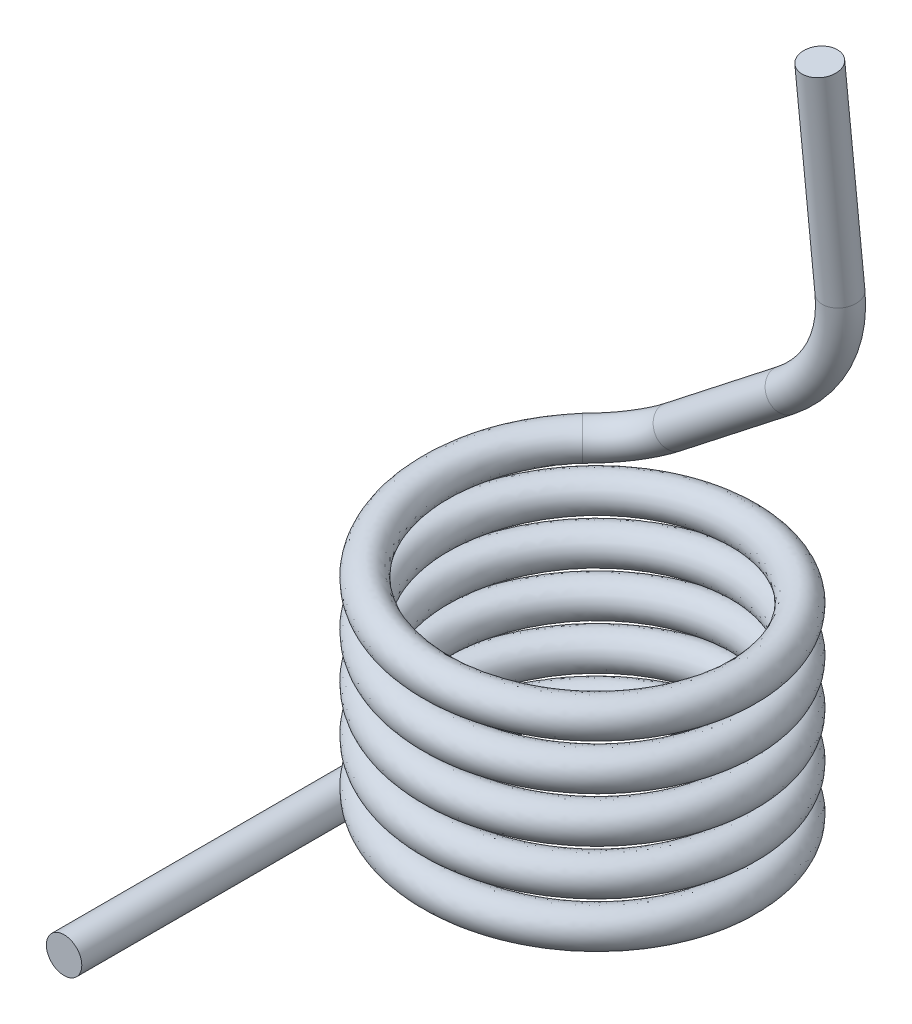
SolidWorks part; units mm, degrees
ref_plane "Front Plane" through (0, 0, 0) normal (0, 0, 1) x (1, 0, 0)
ref_plane "Top Plane" through (0, 0, 0) normal (0, 1, 0) x (1, 0, 0)
ref_plane "Right Plane" through (0, 0, 0) normal (1, 0, 0) x (0, 0, -1)
sketch "Sketch1" plane through (0, 0, 0) normal (0, 1, 0) x (1, 0, 0)
  circle A0 centre (0, 0) radius 24.13
  dimension "D1" = 48.26
curve "Helix/Spiral1" pitch 7.1437 height 36.6117 turns 5.125
sketch "Sketch2" plane through (0, 0, 0) normal (0, 0, 1) x (1, 0, 0)
  circle A0 centre (-24.13, 0) radius 2.7781
  spline S0 degree 3 poles (-24.13, 0) (-24.13, 0.1096) (-23.4483, 0.33) (-20.4662, 0.6596) (-15.7737, 0.9895) (-9.763, 1.3193) (-2.9364, 1.6492) (4.1356, 1.979) (10.862, 2.3088) (16.6806, 2.6387) (21.1053, 2.9685) (23.7661, 3.2984) (24.4408, 3.6282) (23.073, 3.958) (19.777, 4.2879) (14.8281, 4.6177) (8.6401, 4.9475) (1.73, 5.2774) (-5.3246, 5.6072) (-11.9343, 5.937) (-17.5466, 6.2669) (-21.6926, 6.5967) (-24.0256, 6.9265) (-24.3509, 7.2564) (-22.6411, 7.5862) (-19.0392, 7.916) (-13.8462, 8.2459) (-7.496, 8.5757) (-0.5194, 8.9056) (6.5006, 9.2354) (12.9774, 9.5652) (18.3696, 9.8951) (22.2266, 10.2249) (24.2262, 10.5547) (24.2012, 10.8846) (22.1537, 11.2144) (18.2547, 11.5442) (12.8302, 11.8741) (6.3335, 12.2039) (-0.6925, 12.5337) (-7.6606, 12.8636) (-13.9886, 13.1934) (-19.1475, 13.5232) (-22.7062, 13.8531) (-24.3674, 14.1829) (-23.9922, 14.5128) (-21.6119, 14.8426) (-17.4255, 15.1724) (-11.7828, 15.5023) (-5.1555, 15.8321) (1.9027, 16.1619) (8.8019, 16.4918) (14.9655, 16.8216) (19.8784, 17.1514) (23.1301, 17.4813) (24.4488, 17.8111) (23.7243, 18.1409) (21.0171, 18.4708) (16.5535, 18.8006) (10.7066, 19.1304) (3.9648, 19.4603) (-3.1082, 19.7901) (-9.9215, 20.12) (-15.9057, 20.4498) (-20.5606, 20.7796) (-23.4973, 21.1095) (-24.4702, 21.4393) (-23.3982, 21.7691) (-20.3708, 22.099) (-15.641, 22.4288) (-9.604, 22.7586) (-2.7644, 23.0885) (4.3061, 23.4183) (11.0169, 23.7481) (16.8069, 24.078) (21.1924, 24.4078) (23.8068, 24.7376) (24.4316, 25.0675) (23.0147, 25.3973) (19.6745, 25.7272) (14.69, 26.057) (8.4779, 26.3868) (1.5573, 26.7167) (-5.4935, 27.0465) (-12.0852, 27.3763) (-17.6669, 27.7062) (-21.7721, 28.036) (-24.0579, 28.3658) (-24.3331, 28.6957) (-22.5748, 29.0255) (-18.9299, 29.3553) (-13.7031, 29.6852) (-7.331, 30.015) (-0.3463, 30.3448) (6.6674, 30.6747) (13.1238, 31.0045) (18.4835, 31.3344) (22.2985, 31.6642) (24.25, 31.994) (24.175, 32.3239) (22.0796, 32.6537) (18.139, 32.9835) (12.6825, 33.3134) (6.1661, 33.6432) (-0.8656, 33.973) (-7.8249, 34.3029) (-14.1303, 34.6327) (-19.2548, 34.9625) (-22.7702, 35.2924) (-24.3829, 35.6222) (-23.9568, 35.9521) (-21.5328, 36.2817) (-18.7067, 36.5022) (-17.0625, 36.6117) knots 0 0 0 0 0.009009 0.018018 0.027027 0.036036 0.045045 0.054054 0.063063 0.072072 0.081081 0.09009 0.099099 0.108108 0.117117 0.126126 0.135135 0.144144 0.153153 0.162162 0.171171 0.18018 0.189189 0.198198 0.207207 0.216216 0.225225 0.234234 0.243243 0.252252 0.261261 0.27027 0.279279 0.288288 0.297297 0.306306 0.315315 0.324324 0.333333 0.342342 0.351351 0.36036 0.369369 0.378378 0.387387 0.396396 0.405405 0.414414 0.423423 0.432432 0.441441 0.45045 0.459459 0.468468 0.477477 0.486486 0.495495 0.504505 0.513514 0.522523 0.531532 0.540541 0.54955 0.558559 0.567568 0.576577 0.585586 0.594595 0.603604 0.612613 0.621622 0.630631 0.63964 0.648649 0.657658 0.666667 0.675676 0.684685 0.693694 0.702703 0.711712 0.720721 0.72973 0.738739 0.747748 0.756757 0.765766 0.774775 0.783784 0.792793 0.801802 0.810811 0.81982 0.828829 0.837838 0.846847 0.855856 0.864865 0.873874 0.882883 0.891892 0.900901 0.90991 0.918919 0.927928 0.936937 0.945946 0.954955 0.963964 0.972973 0.981982 0.990991 1 1 1 1 construction
  dimension "D1" = 5.5562
sweep "Sweep1" add profiles "Sketch2" path "Helix/Spiral1"
sketch "Sketch4" plane through (0, 0, 0) normal (0, 0, 1) x (1, 0, 0)
  circle A0 centre (-24.13, 0) radius 2.7781
  circle A2 centre (-24.13, 0) radius 2.7781 construction
  point P5 (0, 0)
extrude "Boss-Extrude1" add sketch "Sketch4" along normal blind 57.15
sketch3d "3DSketch1"
  line L0 (-7.7297, 40.3722, -21.9195) -> (8.3375, 52.6145, -23.4125)
  line L1 (-17.0625, 36.6125, -17.0625) -> (8.3375, 36.6125, -17.0625) construction
  line L2 (8.3375, 36.6125, -17.0625) -> (8.3375, 52.6145, -17.0625) construction
  line L3 (8.3375, 52.6145, -17.0625) -> (8.3375, 52.6145, -23.4125) construction
  line L4 (17.2275, 70.5433, -23.161) -> (17.2275, 103.4103, -23.161) construction
  line L5 (17.2275, 103.4103, -23.161) -> (17.2275, 103.4103, -19.986) construction
  line L6 (17.2275, 70.5433, -23.161) -> (17.2275, 103.4103, -19.986)
  line L7 (8.3375, 52.6145, -17.0625) -> (17.2275, 52.6145, -17.0625) construction
  line L8 (17.2275, 52.6145, -17.0625) -> (17.2275, 70.5433, -17.0625) construction
  line L9 (17.2275, 70.5433, -17.0625) -> (17.2275, 70.5433, -23.161) construction
  arc A1 (-17.0625, 36.6125, -17.0625) -> (-7.7297, 40.3722, -21.9195) centre (-11.2792, 46.3284, -11.2792) ccw
  circle A3 centre (-17.0625, 36.6125, -17.0625) radius 2.7781 construction
  arc A5 (8.3375, 52.6145, -23.4125) -> (17.2275, 70.5433, -23.161) centre (-4.6975, 70.1939, -19.5436) ccw
  point P2 (-4.4091, 38.1496, -4.4091)
  point P7 (-15.0981, 36.6125, -19.0269)
  point P14 (-1.0633, 68.0857, 2.2798)
  point P16 (10.979, 59.9045, -19.926)
  point P17 (13.6268, 52.6145, -16.6135)
  dimension "D3" = 25.4
  dimension "D1" = 12.7
  dimension "D2" = 16.002
  dimension "D4" = 6.35
  dimension "D5" = 33.02
  dimension "D6" = 3.175
  dimension "D7" = 34.29
sketch "Sketch5" plane through (0, 0, 0) normal (0.7071, 0, -0.7071) x (-0.7071, 0, -0.7071)
  circle A0 centre (24.13, 36.6125) radius 2.7781
  circle A1 centre (24.13, 36.6125) radius 2.7781 construction
sweep "Sweep2" add profiles "Sketch5" path "3DSketch1"
ref_plane "Plane1" through (0, 40.894, 0) normal (0, 1, 0) x (1, 0, 0)
